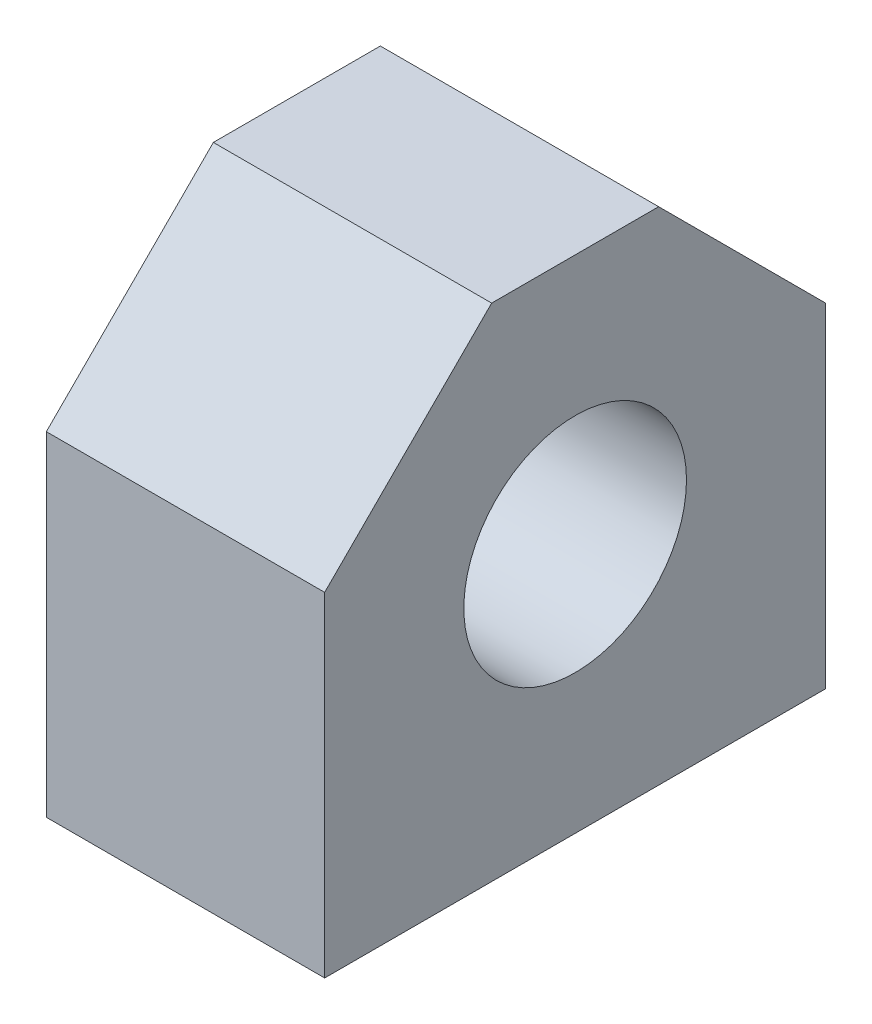
SolidWorks part; units mm, degrees
material "6061 Alloy"
ref_plane "Front Plane" through (0, 0, 0) normal (0, 0, 1) x (1, 0, 0)
ref_plane "Top Plane" through (0, 0, 0) normal (0, 1, 0) x (1, 0, 0)
ref_plane "Right Plane" through (0, 0, 0) normal (1, 0, 0) x (0, 0, -1)
sketch "Sketch2" plane through (0, 0, 0) normal (1, 0, 0) x (0, 0, -1)
  line L1 (0, 0) -> (57.15, 0)
  line L2 (0, 0) -> (0, 57.15)
  line L3 (0, 57.15) -> (57.15, 57.15)
  line L4 (57.15, 0) -> (57.15, 57.15)
  dimension "D1" = 57.15
extrude "Boss-Extrude2" add sketch "Sketch2" along normal blind 31.75
sketch "Sketch3" plane through (31.75, 0, 0) normal (1, 0, 0) x (0, 0, -1)
  line L0 (0, 57.15) -> (57.15, 0) construction
  circle A0 centre (28.575, 28.575) radius 12.7
  dimension "D1" = 25.4
extrude "Cut-Extrude1" cut sketch "Sketch3" against normal through all
sketch "Sketch4" plane through (0, 0, 0) normal (-1, 0, 0) x (0, 0, 1)
  line L0 (-28.575, 42.8625) -> (-28.575, 14.2875) construction
  line L1 (-35.4948, 42.8625) -> (-21.6552, 42.8625)
  line L2 (-21.6552, 14.2875) -> (-35.4948, 14.2875)
  circle A0 centre (-28.575, 28.575) radius 12.7 construction
  arc A1 (-35.4948, 42.8625) -> (-35.4948, 14.2875) centre (-28.575, 28.575) ccw
  arc A2 (-21.6552, 42.8625) -> (-21.6552, 14.2875) centre (-28.575, 28.575) cw
  point P2 (-28.575, 28.575)
  dimension "D2" = 15.875
  dimension "D1" = 28.575
extrude "Cut-Extrude2" cut sketch "Sketch4" against normal blind 2.54
fillet "Fillet1" radius 3.175 4 edges at (1.27, 14.2875, -35.4948) (1.27, 14.2875, -21.6552) (1.27, 42.8625, -21.6552) (1.27, 42.8625, -35.4948)
chamfer "Chamfer1" distance 19.05 distance2 19.05 2 edges at (15.875, 57.15, -57.15) (15.875, 57.15, 0)
